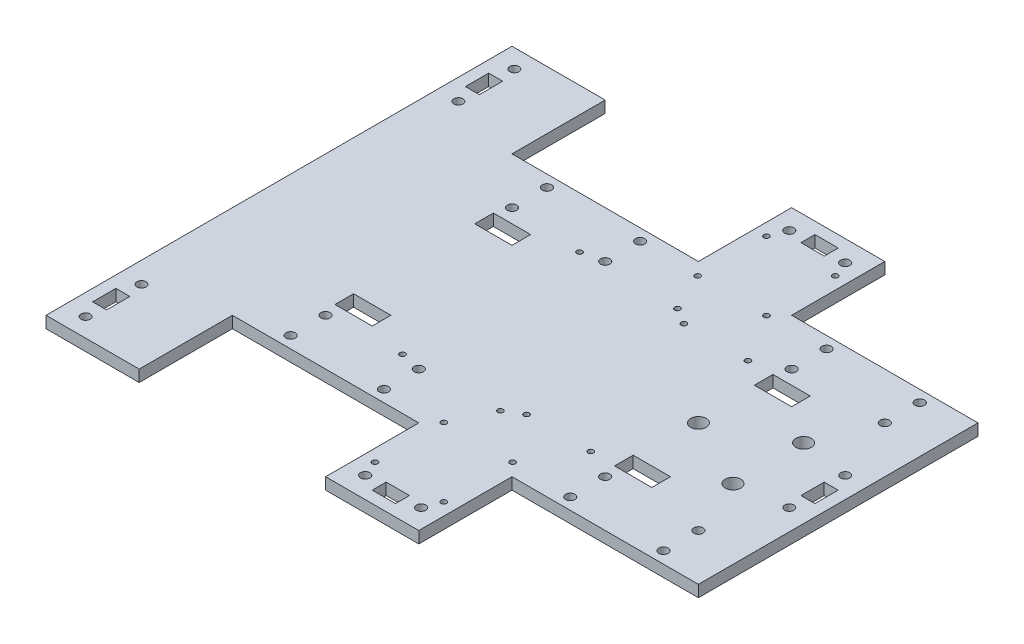
SolidWorks part; units mm, degrees
ref_plane "Front Plane" through (0, 0, 0) normal (0, 0, 1) x (1, 0, 0)
ref_plane "Top Plane" through (0, 0, 0) normal (0, 1, 0) x (1, 0, 0)
ref_plane "Right Plane" through (0, 0, 0) normal (1, 0, 0) x (0, 0, -1)
sketch "Sketch1" plane through (0, 0, 0) normal (0, 1, 0) x (1, 0, 0)
  line L0 (0, 0) -> (0, 152.4) construction
  line L13 (0, 152.4) -> (101.6, 152.4)
  line L16 (152.4, 152.4) -> (254, 152.4)
  line L17 (254, 152.4) -> (254, 0)
  line L18 (254, 0) -> (152.4, 0)
  line L21 (101.6, 0) -> (0, 0)
  line L22 (101.6, 152.4) -> (101.6, 203.2)
  line L23 (101.6, 203.2) -> (152.4, 203.2)
  line L24 (152.4, 203.2) -> (152.4, 152.4)
  line L25 (101.6, 0) -> (101.6, -50.8)
  line L26 (101.6, -50.8) -> (152.4, -50.8)
  line L27 (152.4, -50.8) -> (152.4, 0)
  line L28 (0, 152.4) -> (0, 203.2)
  line L29 (0, 203.2) -> (-50.8, 203.2)
  line L30 (-50.8, 203.2) -> (-50.8, -50.8)
  line L31 (-50.8, -50.8) -> (0, -50.8)
  line L32 (0, -50.8) -> (0, 0)
  dimension "D1" = 254
  dimension "D2" = 152.4
  dimension "D3" = 101.6
  dimension "D4" = 50.8
  dimension "D5" = 50.8
  dimension "D6" = 50.8
  dimension "D7" = 50.8
extrude "Boss-Extrude1" add sketch "Sketch1" along normal blind 6.35
sketch "Sketch2" plane through (0, 6.35, 0) normal (0, 1, 0) x (1, 0, 0)
  line L0 (152.4, 203.2) -> (101.6, 203.2) construction
  line L1 (133.35, 189.23) -> (120.65, 189.23)
  line L2 (133.35, 189.23) -> (133.35, 196.85)
  line L3 (133.35, 196.85) -> (120.65, 196.85)
  line L4 (120.65, 189.23) -> (120.65, 196.85)
  line L5 (254, 0) -> (254, 152.4) construction
  point P6 (127, 203.2)
  dimension "D1" = 12.7
  dimension "D2" = 7.62
  dimension "D3" = 6.35
  dimension "D4" = 19.05
extrude "Cut-Extrude1" cut sketch "Sketch2" against normal through all contours L2 L3 L4 L1
sketch "Sketch3" plane through (0, 0, 0) normal (0, -1, 0) x (1, 0, 0)
  line L0 (0, -76.2) -> (254, -76.2) construction
  line L2 (254, 0) -> (254, -152.4) construction
  line L3 (254, -152.4) -> (152.4, -152.4) construction
  line L4 (101.6, 50.8) -> (152.4, 50.8) construction
  line L5 (127, 50.8) -> (127, -203.2) construction
  line L6 (152.4, -203.2) -> (101.6, -203.2) construction
  line L7 (0, 0) -> (0, -152.4) construction
  line L8 (50.8, 0) -> (50.8, -152.4) construction
  line L9 (0, 0) -> (101.6, 0) construction
  line L10 (101.6, -152.4) -> (0, -152.4) construction
  circle A0 centre (228.6, -146.05) radius 2.54
  circle A1 centre (177.8, -146.05) radius 2.54
  circle A2 centre (228.6, -127) radius 2.54
  circle A3 centre (177.8, -127) radius 2.54
  circle A4 centre (177.8, -25.4) radius 2.54
  circle A5 centre (228.6, -25.4) radius 2.54
  circle A6 centre (177.8, -6.35) radius 2.54
  circle A7 centre (228.6, -6.35) radius 2.54
  circle A8 centre (25.4, -6.35) radius 2.54
  circle A9 centre (76.2, -6.35) radius 2.54
  circle A10 centre (25.4, -25.4) radius 2.54
  circle A11 centre (76.2, -25.4) radius 2.54
  circle A12 centre (76.2, -127) radius 2.54
  circle A13 centre (25.4, -127) radius 2.54
  circle A14 centre (76.2, -146.05) radius 2.54
  circle A15 centre (25.4, -146.05) radius 2.54
  circle A16 centre (142.24, -191.77) radius 2.54
  circle A17 centre (111.76, -191.77) radius 2.54
  circle A18 centre (142.24, 39.37) radius 2.54
  circle A19 centre (111.76, 39.37) radius 2.54
  point P15 (0, -76.2)
  dimension "D1" = 5.08
  dimension "D4" = 5.08
  dimension "D6" = 15.24
  dimension "D2" = 50.8
  dimension "D3" = 25.4
  dimension "D5" = 6.35
  dimension "D7" = 19.05
  dimension "D8" = 11.43
extrude "Cut-Extrude2" cut sketch "Sketch3" against normal through all
hole_wizard "Ø5.0mm Dowel Hole1" positions "3DSketch1" profile "Sketch5" hole size "Ø5.0" standard "ANSI Metric" end condition through all
sketch3d "3DSketch1"
  line L0 (101.6, 6.35, -203.2) -> (101.6, 6.35, -152.4) construction
  line L1 (0, 6.35, -203.2) -> (-50.8, 6.35, -203.2) construction
  line L2 (-50.8, 6.35, 50.8) -> (0, 6.35, 50.8) construction
  line L3 (152.4, 6.35, -203.2) -> (101.6, 6.35, -203.2) construction
  line L4 (-50.8, 6.35, -203.2) -> (-50.8, 6.35, 50.8) construction
  line L5 (254, 6.35, 0) -> (254, 6.35, -152.4) construction
  line L6 (254, 6.35, -152.4) -> (152.4, 6.35, -152.4) construction
  circle A0 centre (142.24, 6.35, -191.77) radius 2.54 construction
  circle A1 centre (111.76, 6.35, -191.77) radius 2.54 construction
  point P0 (-39.37, 6.35, 40.64)
  point P2 (-39.37, 6.35, 10.16)
  point P4 (-39.37, 6.35, -162.56)
  point P6 (-39.37, 6.35, -193.04)
  point P11 (242.57, 6.35, -60.96)
  point P13 (242.57, 6.35, -91.44)
  point P18 (142.24, 3.81, -191.77)
  point P21 (111.76, 3.81, -191.77)
  dimension "D1" = 30.48
  dimension "D5" = 10.16
  dimension "D8" = 11.43
  dimension "D2" = 30.48
  dimension "D3" = 30.48
  dimension "D4" = 30.48
  dimension "D6" = 10.16
  dimension "D7" = 10.16
  dimension "D9" = 11.43
  dimension "D10" = 11.43
  dimension "D11" = 60.96
sketch "Sketch5" plane through (-39.37, 6.35, 40.64) normal (1, 0, 0) x (0, 0, 1)
  line L0 (0, 0) -> (0, 6.35)
  line L1 (0, 6.35) -> (2.5, 6.35)
  line L2 (2.5, 6.35) -> (2.5, 0)
  line L5 (2.5, 0) -> (0, 0)
  line L11 (0, -6.35) -> (0, 107.95) construction
  dimension "Thru Hole Dia." = 5
  dimension "Thru Hole Depth" = 6.35
sketch "Sketch6" plane through (0, 6.35, 0) normal (0, 1, 0) x (1, 0, 0)
  line L0 (133.35, 189.23) -> (133.35, 196.85) construction
  line L1 (133.35, -44.45) -> (120.65, -44.45)
  line L2 (133.35, -44.45) -> (133.35, -36.83)
  line L3 (133.35, -36.83) -> (120.65, -36.83)
  line L4 (120.65, -44.45) -> (120.65, -36.83)
  line L5 (-44.45, -31.75) -> (-36.83, -31.75)
  line L6 (-44.45, -31.75) -> (-44.45, -19.05)
  line L7 (-44.45, -19.05) -> (-36.83, -19.05)
  line L8 (-36.83, -31.75) -> (-36.83, -19.05)
  line L9 (-44.45, 171.45) -> (-36.83, 171.45)
  line L10 (-44.45, 171.45) -> (-44.45, 184.15)
  line L11 (-44.45, 184.15) -> (-36.83, 184.15)
  line L12 (-36.83, 171.45) -> (-36.83, 184.15)
  line L13 (247.65, 69.85) -> (240.03, 69.85)
  line L14 (247.65, 69.85) -> (247.65, 82.55)
  line L15 (247.65, 82.55) -> (240.03, 82.55)
  line L16 (240.03, 69.85) -> (240.03, 82.55)
  line L17 (133.35, 189.23) -> (120.65, 189.23) construction
  line L18 (-50.8, 203.2) -> (-50.8, -50.8) construction
  line L19 (101.6, -50.8) -> (152.4, -50.8) construction
  line L20 (254, 0) -> (254, 152.4) construction
  line L21 (0, 203.2) -> (-50.8, 203.2) construction
  line L22 (101.6, 0) -> (101.6, -50.8) construction
  line L23 (-50.8, -50.8) -> (0, -50.8) construction
  line L24 (254, 152.4) -> (152.4, 152.4) construction
  point P28 (120.65, -40.64)
  point P33 (0, 0)
  point P34 (0, 0)
  point P35 (0, 0)
  dimension "D1" = 6.35
  dimension "D2" = 6.35
  dimension "D3" = 6.35
  dimension "D4" = 19.05
  dimension "D5" = 19.05
  dimension "D6" = 19.05
  dimension "D7" = 69.85
extrude "Cut-Extrude3" cut sketch "Sketch6" against normal through all
sketch "Sketch7" plane through (0, 6.35, 0) normal (0, 1, 0) x (1, 0, 0)
  line L1 (43.18, 33.02) -> (22.86, 33.02)
  line L2 (43.18, 33.02) -> (43.18, 43.18)
  line L3 (43.18, 43.18) -> (22.86, 43.18)
  line L4 (22.86, 33.02) -> (22.86, 43.18)
  line L5 (43.18, 109.22) -> (22.86, 109.22)
  line L6 (43.18, 109.22) -> (43.18, 119.38)
  line L7 (43.18, 119.38) -> (22.86, 119.38)
  line L8 (22.86, 109.22) -> (22.86, 119.38)
  line L9 (195.58, 33.02) -> (175.26, 33.02)
  line L10 (195.58, 33.02) -> (195.58, 43.18)
  line L11 (195.58, 43.18) -> (175.26, 43.18)
  line L12 (175.26, 33.02) -> (175.26, 43.18)
  line L13 (195.58, 109.22) -> (175.26, 109.22)
  line L14 (195.58, 109.22) -> (195.58, 119.38)
  line L15 (195.58, 119.38) -> (175.26, 119.38)
  line L16 (175.26, 109.22) -> (175.26, 119.38)
  circle A0 centre (25.4, 127) radius 2.54 construction
  circle A1 centre (25.4, 25.4) radius 2.54 construction
  circle A2 centre (177.8, 127) radius 2.54 construction
  dimension "D6" = 2.54
  dimension "D1" = 10.16
  dimension "D2" = 7.62
  dimension "D3" = 20.32
  dimension "D4" = 7.62
  dimension "D5" = 2.54
extrude "Cut-Extrude4" cut sketch "Sketch7" against normal through all
hole_wizard "Ø3.0mm Dowel Hole1" positions "3DSketch2" profile "Sketch8" hole size "Ø3.0" standard "ANSI Metric" end condition through all
sketch3d "3DSketch2"
  line L0 (152.4, 6.35, -203.2) -> (101.6, 6.35, -203.2) construction
  line L1 (101.6, 6.35, 50.8) -> (152.4, 6.35, 50.8) construction
  line L2 (-50.8, 6.35, -203.2) -> (-50.8, 6.35, 50.8) construction
  line L3 (-50.8, 6.35, 50.8) -> (0, 6.35, 50.8) construction
  point P0 (161.925, 6.35, -33.3375)
  point P2 (161.925, 6.35, -119.0625)
  point P4 (127, 6.35, -119.0625)
  point P6 (127, 6.35, -33.3375)
  point P8 (118.11, 6.35, -124.46)
  point P10 (118.11, 6.35, -27.94)
  point P12 (64.77, 6.35, -27.94)
  point P14 (64.77, 6.35, -124.46)
  point P16 (108.1931, 6.35, -182.88)
  point P18 (108.1931, 6.35, -145.38)
  point P20 (145.6931, 6.35, -145.38)
  point P22 (145.6931, 6.35, -182.88)
  point P24 (145.6931, 6.35, 30.48)
  point P26 (108.1931, 6.35, 30.48)
  point P28 (108.1931, 6.35, -7.02)
  point P30 (145.6931, 6.35, -7.02)
  dimension "D1" = 37.5
  dimension "D2" = 37.5
  dimension "D3" = 37.5
  dimension "D4" = 20.32
  dimension "D5" = 20.32
  dimension "D6" = 34.925
  dimension "D7" = 85.725
  dimension "D8" = 96.52
  dimension "D9" = 53.34
  dimension "D10" = 115.57
  dimension "D11" = 78.74
  dimension "D12" = 84.1375
  dimension "D13" = 177.8
sketch "Sketch8" plane through (161.925, 6.35, -33.3375) normal (1, 0, 0) x (0, 0, 1)
  line L0 (0, 0) -> (0, 6.35)
  line L1 (0, 6.35) -> (1.5, 6.35)
  line L2 (1.5, 6.35) -> (1.5, 0)
  line L5 (1.5, 0) -> (0, 0)
  line L11 (0, -6.35) -> (0, 107.95) construction
  dimension "Thru Hole Dia." = 3
  dimension "Thru Hole Depth" = 6.35
hole_wizard "Ø8.0mm Dowel Hole1" positions "3DSketch3" profile "Sketch9" hole size "Ø8.0" standard "ANSI Metric" end condition through all
sketch3d "3DSketch3"
  line L3 (254, 6.35, 0) -> (254, 6.35, -152.4) construction
  line L4 (215.9, 6.35, -56.95) -> (215.9, 6.35, 0) construction
  line L5 (152.4, 6.35, 0) -> (254, 6.35, 0) construction
  line L7 (215.9, 6.35, -95.45) -> (215.9, 6.35, -152.4) construction
  line L8 (254, 6.35, -152.4) -> (152.4, 6.35, -152.4) construction
  line L9 (177.8, 6.35, -76.2) -> (215.9, 6.35, -95.45) construction
  line L11 (177.8, 6.35, -76.2) -> (215.9, 6.35, -56.95) construction
  point P0 (215.9, 6.35, -56.95)
  point P2 (215.9, 6.35, -95.45)
  point P4 (177.8, 6.35, -76.2)
  dimension "D4" = 38.1
  dimension "D1" = 38.5
  dimension "D3" = 76.2
sketch "Sketch9" plane through (215.9, 6.35, -56.95) normal (1, 0, 0) x (0, 0, 1)
  line L0 (0, 0) -> (0, 6.35)
  line L1 (0, 6.35) -> (4.25, 6.35)
  line L2 (4.25, 6.35) -> (4.25, 0)
  line L5 (4.25, 0) -> (0, 0)
  line L11 (0, -6.35) -> (0, 107.95) construction
  dimension "Thru Hole Dia." = 8.5
  dimension "Thru Hole Depth" = 6.35
sketch "Sketch10" plane through (0, 6.35, 0) normal (0, 1, 0) x (1, 0, 0)
  line L0 (152.4, 0) -> (254, 0) construction
  line L1 (234.95, 56.261) -> (213.614, 56.261)
  line L2 (234.95, 56.261) -> (234.95, 96.901)
  line L3 (234.95, 96.901) -> (213.614, 96.901)
  line L4 (213.614, 56.261) -> (213.614, 96.901)
  line L5 (240.03, 82.55) -> (240.03, 69.85) construction
  dimension "D1" = 40.64
  dimension "D2" = 21.336
  dimension "D3" = 56.261
  dimension "D4" = 5.08
extrude "Cut-Extrude5" [suppressed] cut sketch "Sketch10" against normal through all
